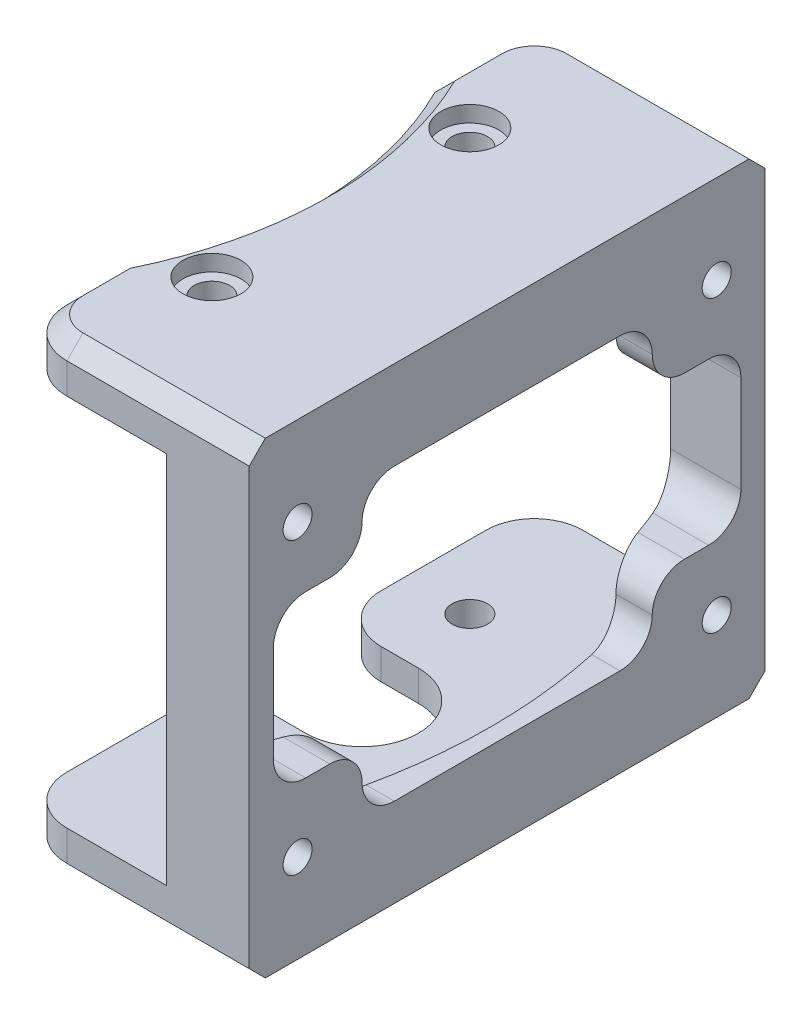
SolidWorks part; units mm, degrees
ref_plane "Спереди" through (0, 0, 0) normal (0, 0, 1) x (1, 0, 0)
ref_plane "Сверху" through (0, 0, 0) normal (0, 1, 0) x (1, 0, 0)
ref_plane "Справа" through (0, 0, 0) normal (1, 0, 0) x (0, 0, -1)
sketch "Эскиз1" plane through (0, 0, 0) normal (0, 1, 0) x (1, 0, 0)
  line L1 (19.6854, 16) -> (34, 16)
  line L2 (19.6854, 16) -> (19.6854, -16)
  line L3 (19.6854, -16) -> (34, -16)
  line L4 (34, 16) -> (34, -16)
  line L5 (19.6854, 16) -> (34, -16) construction
  line L6 (19.6854, -16) -> (34, 16) construction
  line L7 (23.6854, 8) -> (23.6854, -8) construction
  circle A0 centre (0, 0) radius 25 construction
  circle A1 centre (23.6854, 8) radius 1.1
  circle A2 centre (23.6854, -8) radius 1.1
  point P3 (26.8427, 0)
  dimension "D1" = 50
  dimension "D6" = 2.2
  dimension "D7" = 2.2
  dimension "D2" = 32
  dimension "D3" = 34
  dimension "D4" = 16
  dimension "D5" = 4
extrude "Бобышка-Вытянуть1" add sketch "Эскиз1" along normal mid plane 29
sketch "Эскиз2" plane through (0, 0, 0) normal (0, 1, 0) x (1, 0, 0)
  circle A0 centre (0, 0) radius 33
  dimension "D1" = 66
extrude "Вырез-Вытянуть1" cut sketch "Эскиз2" against normal mid plane 23.2
sketch "Эскиз3" plane through (34, 0, 0) normal (1, 0, 0) x (0, 0, -1)
  line L0 (-13, 5) -> (-9, 5)
  line L1 (13, 9) -> (-13, 9) construction
  line L2 (13, 9) -> (13, -9) construction
  line L3 (13, -9) -> (-13, -9) construction
  line L4 (-13, 9) -> (-13, -9) construction
  line L5 (13, 9) -> (-13, -9) construction
  line L6 (13, -9) -> (-13, 9) construction
  line L7 (-9, 5) -> (-9, 9)
  line L8 (-13, 0) -> (13, 0) construction
  line L9 (0, 9) -> (0, -9) construction
  line L10 (-9, -5) -> (-9, -9)
  line L11 (-13, -5) -> (-9, -5)
  line L12 (-13, 5) -> (-13, -5)
  line L13 (9, -5) -> (9, -9)
  line L14 (13, -5) -> (9, -5)
  line L15 (13, 5) -> (13, -5)
  line L16 (13, 5) -> (9, 5)
  line L17 (9, 5) -> (9, 9)
  line L18 (-9, 9) -> (9, 9)
  line L19 (9, -9) -> (-9, -9)
  circle A0 centre (-13, 9) radius 0.9
  circle A1 centre (-13, -9) radius 0.9
  circle A2 centre (13, 9) radius 0.9
  circle A3 centre (13, -9) radius 0.9
  point P0 (0, 0)
  dimension "D5" = 1.8
  dimension "D6" = 1.8
  dimension "D7" = 1.8
  dimension "D8" = 1.8
  dimension "D1" = 18
  dimension "D2" = 26
  dimension "D3" = 4
  dimension "D4" = 4
extrude "Вырез-Вытянуть2" cut sketch "Эскиз3" against normal through all
sketch "Эскиз4" plane through (0, -14.5, 0) normal (0, -1, 0) x (1, 0, 0)
  line L0 (19.6854, -16) -> (19.6854, 16) construction
  line L1 (25, 3.5) -> (19.6854, 3.5)
  line L2 (25, 3.5) -> (25, -3.5) construction
  line L3 (25, -3.5) -> (19.6854, -3.5)
  line L4 (19.6854, 3.5) -> (19.6854, -3.5)
  circle A0 centre (0, 0) radius 25 construction
  circle A1 centre (25, 0) radius 3.5
  line M9 (19.6854, 16) -> (19.6854, -16)
  dimension "D1" = 50
  dimension "D2" = 7
extrude "Вырез-Вытянуть3" cut sketch "Эскиз4" against normal up to next contours A1 L1 L3 M9 | A1 region at (21.0872, -14.5, 0) region at (25, -14.5, 0)
sketch "Эскиз6" plane through (0, 14.5, 0) normal (0, 1, 0) x (1, 0, 0)
  circle A0 centre (0, 0) radius 22
  dimension "D1" = 44
extrude "Вырез-Вытянуть5" cut sketch "Эскиз6" against normal up to next
sketch "Эскиз7" plane through (34, 0, 0) normal (1, 0, 0) x (0, 0, -1)
  line L0 (-9, 5) -> (-13, 5) construction
  line L1 (14.5, 5) -> (-14.5, 5)
  line L2 (14.5, 5) -> (14.5, -5)
  line L3 (14.5, -5) -> (-14.5, -5)
  line L4 (-14.5, 5) -> (-14.5, -5)
  line L5 (14.5, 5) -> (-14.5, -5) construction
  line L6 (14.5, -5) -> (-14.5, 5) construction
  line L7 (-13, 5) -> (-13, -5) construction
  point P0 (0, 0)
  dimension "D1" = 1.5
extrude "Вырез-Вытянуть6" cut sketch "Эскиз7" against normal through all
fillet "Скругление1" radius 3 6 edges at (19.6854, -13.05, 3.5) (19.6854, -13.05, -3.5) (19.6854, -13.05, -16) (19.6854, 13.05, -16) (19.6854, 13.05, 16) (19.6854, -13.05, 16)
fillet "Скругление3" radius 2 12 edges at (32.8745, -5, 9) (32.8745, -9, 9) (32.8745, -9, -9) (32.8745, -5, -9) (32.8745, 5, -9) (32.8745, 9, -9) (32.8745, 9, 9) (32.8745, 5, 9) (31.8219, 5, -14.5) (31.8219, -5, -14.5) (31.8219, -5, 14.5) (31.8219, 5, 14.5)
chamfer "Фаска2" distance 1 angle 45 17 edges at (28.3427, -14.5, 16) (20.5641, -14.5, 15.1213) (19.6854, -14.5, 9.75) (20.5641, -14.5, 4.3787) (23.8427, -14.5, 3.5) (28.5, -14.5, 0) (23.8427, -14.5, -3.5) (20.5641, -14.5, -4.3787) (19.6854, -14.5, -9.75) (20.5641, -14.5, -15.1213) (28.3427, -14.5, -16) (28.3427, 14.5, 16) (20.5641, 14.5, 15.1213) (20.5641, 14.5, -15.1213) (28.3427, 14.5, -16) (22, 14.5, 0) (19.6854, 14.5, 11.4113)
sketch "Эскиз5" plane through (0, 14.5, 0) normal (0, 1, 0) x (1, 0, 0)
  circle A0 centre (23.6854, 8) radius 1.8
  circle A1 centre (23.6854, -8) radius 1.8
  dimension "D1" = 3.6
  dimension "D2" = 3.6
extrude "Вырез-Вытянуть4" cut sketch "Эскиз5" against normal blind 1
mirror "Зеркальное отражение1" about plane through (0, 0, 0) normal (0, 1, 0) of "Вырез-Вытянуть4"
equation "\"motor_diameter\"= 30"
equation "\"mm_diameter\"= IIF ( \"motor_diameter\" < 34 , 41 , \"motor_diameter\" + 8 )"
equation "\"upper_shafts_diameter\"= 5"
equation "\"upper_shats_length\"= 180"
equation "\"upper_bearing_d1\"= 10"
equation "\"upper_bearing_d2\"= 5"
equation "\"upper_bearing_h\"= 15"
equation "\"lower_shafts_diameter\"= 5"
equation "\"lower_shafts_length\"= 180"
equation "\"lower_bearing_d1\"= 10"
equation "\"lower_bearing_d2\"= 5"
equation "\"lower_bearing_h\"= 15"
equation "\"print_offset\"= 0.2"
equation "\"bh_screws_d\"= 2"
equation "\"bh_screws_h\"= 20"
equation "\"bh_screws_hh_d\"= 3.4"
equation "\"bh_screws_hh_h\"= 2"
equation "\"bh_nut_d\"= 3.8"
equation "\"bh_nut_h\"= 2"
equation "\"motor_screws_d\"= 3"
equation "\"motor_screws_h\"= 16"
equation "\"motor_screws_hh_d\"= 5.5"
equation "\"motor_screws_hh_h\"= 3"
equation "\"plate_hole_distance\"= 25.4"
equation "\"plate_screws_d\"= 6.5"
equation "\"shafts_diameter\"= IIF ( \"mm_diameter\" < 42 , 42 + 8 , \"mm_diameter\" + 8 )"
equation "\"central_hole_diameter\"= 8"
equation "\"bh_thikness\"= 4"
equation "\"ends_screws_d\"= 4"
equation "\"ends_screws_h\"= 16"
equation "\"ends_screws_hh_d\"= 6.7"
equation "\"ends_screws_hh_h\"= 4.1"
equation "\"ends_nut_d\"= 6.8"
equation "\"ends_nut_h\"= 3"
equation "\"system_radius\" = ( \"shafts_diameter\" + 12 + \"bh_thikness\" / 2 ) / 2"
equation "\"encoder_distance\"= \"system_radius\" + 4"
equation "\"tape_position\"= \"encoder_distance\" - 2 + 3.9 + 1.7 / 2"
equation "\"D1@Эскиз1\"=\"shafts_diameter\""
equation "\"D3@Эскиз1\"=\"encoder_distance\"-2"
equation "\"D5@Эскиз1\"=\"bh_thikness\""
equation "\"D6@Эскиз1\"=\"bh_screws_d\"+\"print_offset\""
equation "\"D7@Эскиз1\"=\"bh_screws_d\"+\"print_offset\""
equation "\"D1@Бобышка-Вытянуть1\"=\"upper_bearing_h\"+\"bh_thikness\"*2+6"
equation "\"D1@Эскиз2\"=\"system_radius\"*2+2"
equation "\"D1@Вырез-Вытянуть1\"=\"upper_bearing_h\"+\"bh_thikness\"*2+\"print_offset\""
equation "\"D5@Эскиз3\"=\"bh_screws_d\"-\"print_offset\""
equation "\"D6@Эскиз3\"=\"D5@Эскиз3\""
equation "\"D7@Эскиз3\"=\"D6@Эскиз3\""
equation "\"D8@Эскиз3\"=\"D5@Эскиз3\""
equation "\"D1@Эскиз4\"=\"shafts_diameter\""
equation "\"D2@Эскиз4\"=\"lower_shafts_diameter\"+2"
equation "\"D1@Эскиз5\"=\"bh_screws_hh_d\"+\"print_offset\""
equation "\"D2@Эскиз5\"=\"D1@Эскиз5\""
equation "\"D1@Эскиз6\"= IIF ( \"mm_diameter\" < 42 , 44 , \"mm_diameter\" + 2 )"
